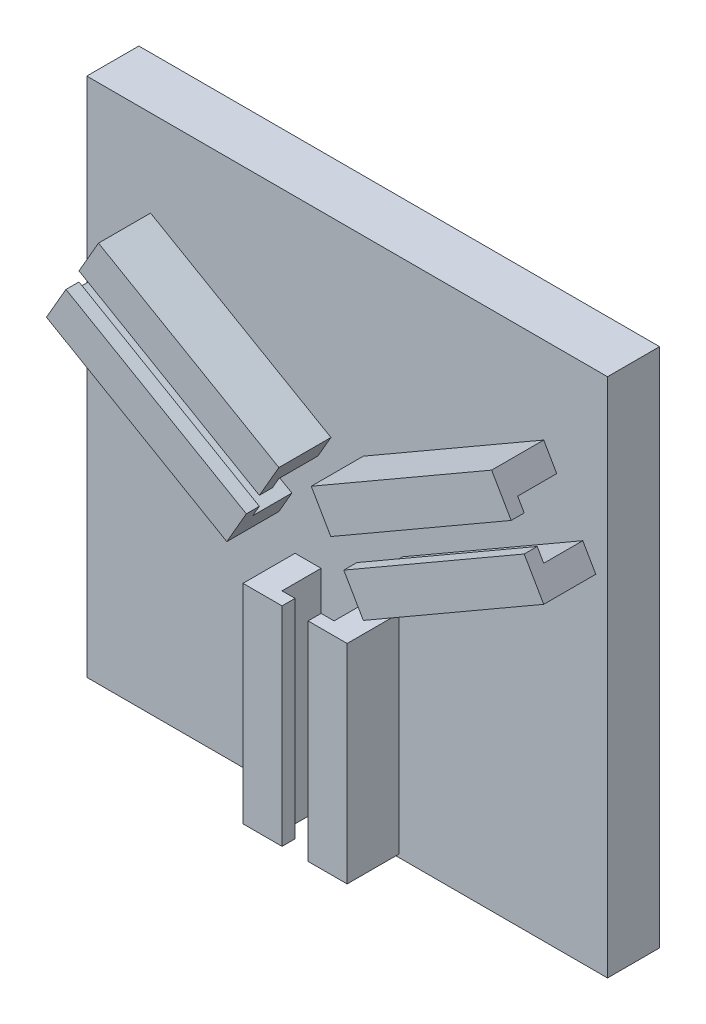
SolidWorks part; units mm, degrees
ref_plane "Front Plane" through (0, 0, 0) normal (0, 0, 1) x (1, 0, 0)
ref_plane "Top Plane" through (0, 0, 0) normal (0, 1, 0) x (1, 0, 0)
ref_plane "Right Plane" through (0, 0, 0) normal (1, 0, 0) x (0, 0, -1)
sketch "Sketch1" plane through (0, 0, 0) normal (0, 0, 1) x (1, 0, 0)
  line L1 (-50, 50) -> (50, 50)
  line L2 (-50, 50) -> (-50, -50)
  line L3 (-50, -50) -> (50, -50)
  line L4 (50, 50) -> (50, -50)
  line L5 (-50, 50) -> (50, -50) construction
  line L6 (-50, -50) -> (50, 50) construction
  point P0 (0, 0)
  dimension "D1" = 100
  dimension "D2" = 100
extrude "Boss-Extrude1" add sketch "Sketch1" along normal blind 10
sketch "Sketch2" plane through (0, 0, 10) normal (0, 0, 1) x (1, 0, 0)
  line L0 (20.144, -11.6301) -> (-36.5149, 21.0819) construction
  line L4 (-20.144, -11.6301) -> (36.5149, 21.0819) construction
  line L5 (0, -11.6301) -> (0, 31.7343) construction
  line L6 (-47.7495, 16.0212) -> (-13.1085, -3.9788)
  line L7 (-47.7495, 16.0212) -> (-37.7495, 33.3417)
  line L8 (-13.1085, -3.9788) -> (-3.1085, 13.3417)
  line L9 (-37.7495, 33.3417) -> (-3.1085, 13.3417)
  line L10 (-47.7495, 16.0212) -> (-3.1085, 13.3417) construction
  line L11 (-13.1085, -3.9788) -> (-37.7495, 33.3417) construction
  line L12 (0, -11.6301) -> (0, -50) construction
  line L13 (-50, -50) -> (50, -50) construction
  point P2 (-25.429, 14.6815)
  dimension "D1" = 40
  dimension "D2" = 20
extrude "Boss-Extrude2" add sketch "Sketch2" along normal blind 10
sketch "Sketch3" plane through (-8.1085, 4.6815, 0) normal (0.866, -0.5, 0) x (0, 0, -1)
  line L0 (-10, 10) -> (-10, -10) construction
  line L5 (-10, -10) -> (-10, 10) construction
  line L6 (-17.5, 5) -> (-10, 5)
  line L11 (-17.5, 5) -> (-17.5, 2.5)
  line L12 (-17.5, -5) -> (-10, -5)
  line L13 (-10, 5) -> (-10, -5)
  line L14 (-17.5, 5) -> (-10, -5) construction
  line L15 (-17.5, -5) -> (-10, 5) construction
  line L16 (-20, 2.5) -> (-17.5, 2.5)
  line L17 (-20, 2.5) -> (-20, -2.5)
  line L18 (-20, -2.5) -> (-17.5, -2.5)
  line L20 (-20, 2.5) -> (-17.5, -2.5) construction
  line L21 (-20, -2.5) -> (-17.5, 2.5) construction
  line L22 (-17.5, -2.5) -> (-17.5, -5)
  line L23 (-20, 0) -> (-10, 0) construction
  point P8 (-13.75, 0)
  point P13 (-18.75, 0)
  point P16 (-10, 0)
  point P17 (-10, 0)
  point P18 (-10, 0)
  dimension "D1" = 10
  dimension "D2" = 7.5
  dimension "D3" = 2.5
  dimension "D4" = 5
extrude "Cut-Extrude1" cut sketch "Sketch3" against normal through all
ref_axis "Axis1" through (0, 0, 0) along (0, 0, 1)
pattern_circular "CirPattern6" count 3 over 360 about axis through (0, 0, 0) along (0, 0, 1) of "Boss-Extrude2", "Cut-Extrude1"
